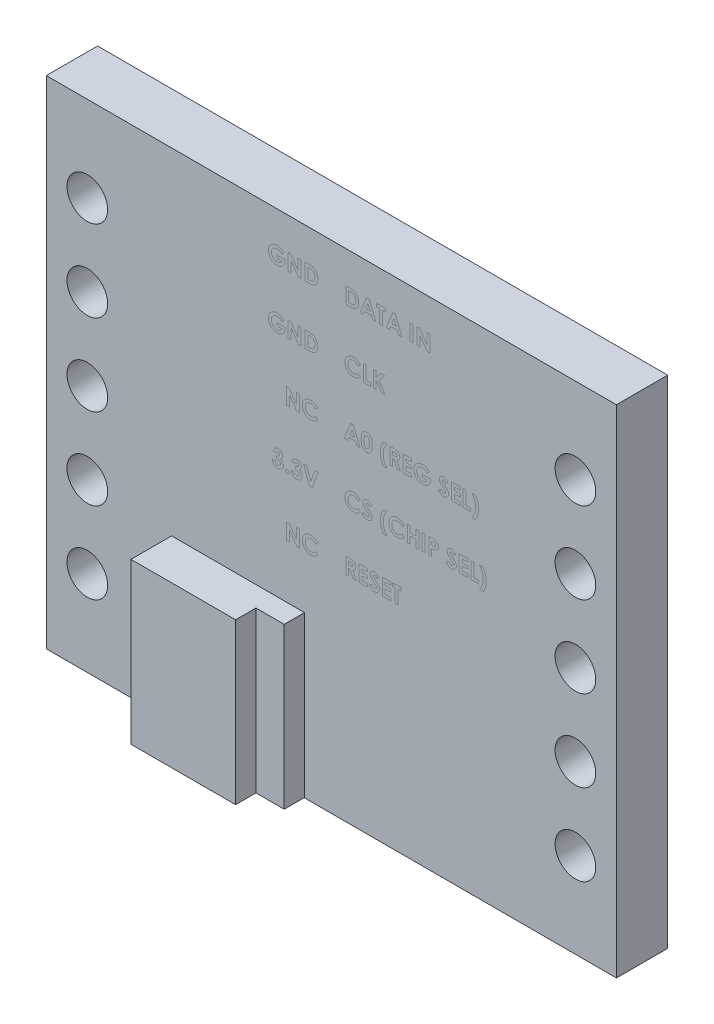
SolidWorks part; units mm, degrees
material "Thornel Mat VMA"
ref_plane "Front Plane" through (0, 0, 0) normal (0, 0, 1) x (1, 0, 0)
ref_plane "Top Plane" through (0, 0, 0) normal (0, 1, 0) x (1, 0, 0)
ref_plane "Right Plane" through (0, 0, 0) normal (1, 0, 0) x (0, 0, -1)
sketch "Sketch1" plane through (0, 0, 0) normal (0, 0, 1) x (1, 0, 0)
  line L0 (-73.8167, -7.75) -> (-56.0167, -7.75) construction
  line L1 (-73.8167, 0) -> (-56.0167, 0)
  line L2 (-73.8167, 0) -> (-73.8167, -15.5)
  line L3 (-73.8167, -15.5) -> (-56.0167, -15.5)
  line L4 (-56.0167, 0) -> (-56.0167, -15.5)
  line L5 (-64.9167, -7.75) -> (-64.9167, 0) construction
  circle A0 centre (-72.5367, -2.67) radius 0.635
  circle A1 centre (-72.5367, -5.21) radius 0.635
  circle A2 centre (-72.5367, -7.75) radius 0.635
  circle A3 centre (-72.5367, -10.29) radius 0.635
  circle A4 centre (-72.5367, -12.83) radius 0.635
  circle A5 centre (-57.2967, -12.83) radius 0.635
  circle A6 centre (-57.2967, -10.29) radius 0.635
  circle A7 centre (-57.2967, -7.75) radius 0.635
  circle A8 centre (-57.2967, -5.21) radius 0.635
  circle A9 centre (-57.2967, -2.67) radius 0.635
  dimension "D3" = 1.27
  dimension "D1" = 17.8
  dimension "D2" = 15.5
  dimension "D5" = 15.24
  dimension "D4" = 5
extrude "Boss-Extrude1" add sketch "Sketch1" along normal blind 1.6002
sketch "Sketch3" plane through (0, 0, 1.6002) normal (0, 0, 1) x (1, 0, 0)
  line L1 (-69.9046, -10.4889) -> (-65.7546, -10.4889)
  line L2 (-69.9046, -10.4889) -> (-69.9046, -15.4889)
  line L3 (-69.9046, -15.4889) -> (-65.7546, -15.4889)
  line L4 (-65.7546, -10.4889) -> (-65.7546, -15.4889)
  dimension "D1" = 5
  dimension "D2" = 4.15
extrude "Boss-Extrude2" add sketch "Sketch3" along normal blind 1.27
sketch "Sketch4" plane through (0, 0, 2.8702) normal (0, 0, 1) x (1, 0, 0)
  line L0 (-65.7546, -10.4889) -> (-69.9046, -10.4889) construction
  line L1 (-66.6367, -10.4889) -> (-65.7546, -10.4889)
  line L2 (-66.6367, -10.4889) -> (-66.6367, -15.4889)
  line L3 (-66.6367, -15.4889) -> (-65.7546, -15.4889)
  line L4 (-65.7546, -10.4889) -> (-65.7546, -15.4889)
extrude "Cut-Extrude1" cut sketch "Sketch4" against normal blind 0.635
sketch "Sketch5" plane through (0, 0, 1.6002) normal (0, 0, 1) x (1, 0, 0)
  line L0 (-64.9167, 0) -> (-64.9167, -15.5) construction
  line L1 (-56.0167, 0) -> (-73.8167, 0) construction
  line L2 (-73.8167, -15.5) -> (-56.0167, -15.5) construction
  line L3 (-64.9167, -1.5113) -> (-56.0167, -1.5113) construction
  line L4 (-56.0167, -15.5) -> (-56.0167, 0) construction
  line L5 (-64.9167, -1.5113) -> (-73.8167, -1.5113) construction
  line L6 (-73.8167, 0) -> (-73.8167, -15.5) construction
  text T0 "<b>  DATA IN</b>\r\n<b>  CLK</b>\r\n<b>  A0 (REG SEL)</b>\r\n<b>  CS (CHIP SEL)</b>\r\n<b>  RESET</b>" font "Century Gothic" height 0.508
  text T1 "<b>  GND  </b>\r\n<b>  GND  </b>\r\n<b>  NC  </b>\r\n<b>  3.3V  </b>\r\n<b>  NC  </b>" font "Century Gothic" height 0.508
wrap "Wrap1" sketch "Sketch5" wrap type scribe source sketch "Sketch5" face at (-57.9317, -5.21, 1.6002)
